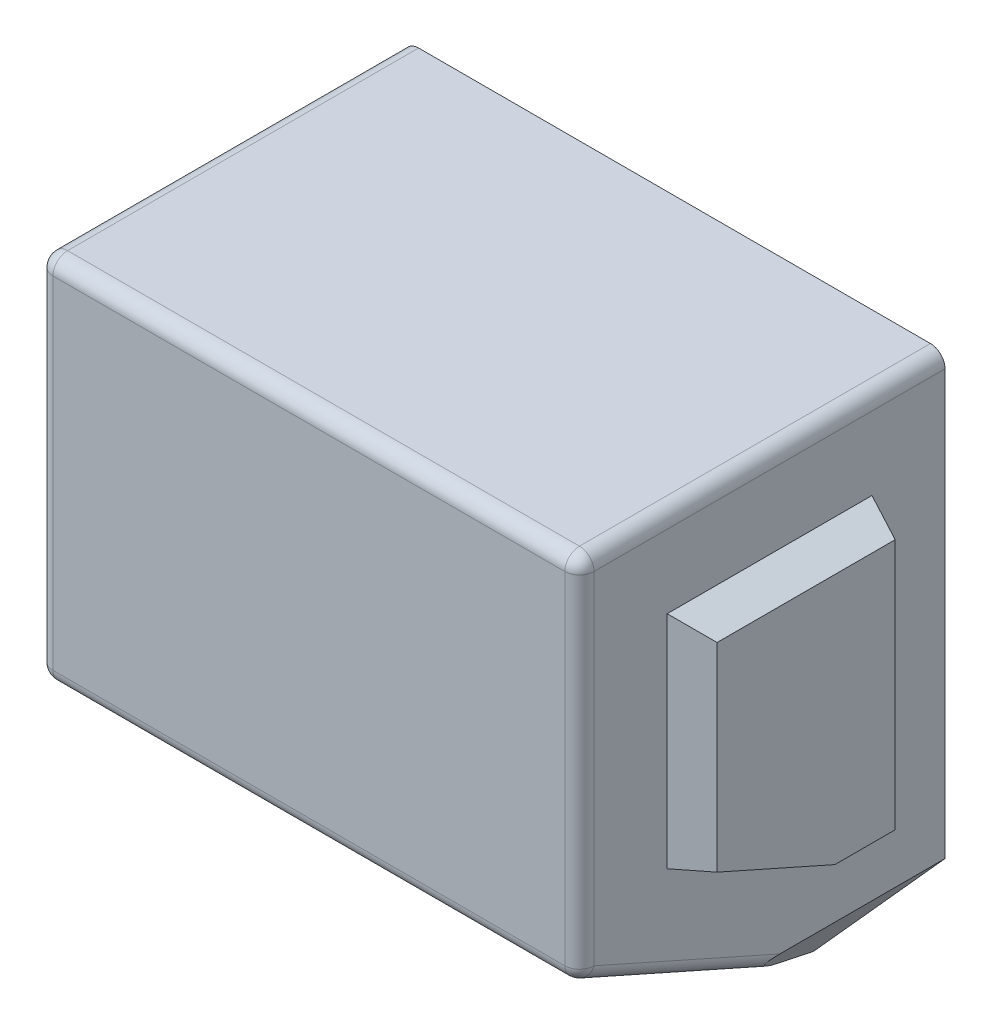
SolidWorks part; units mm, degrees
ref_plane "前视基准面" through (0, 0, 0) normal (0, 0, 1) x (1, 0, 0)
ref_plane "上视基准面" through (0, 0, 0) normal (0, 1, 0) x (1, 0, 0)
ref_plane "右视基准面" through (0, 0, 0) normal (1, 0, 0) x (0, 0, -1)
sketch "草图1" plane through (0, 0, 0) normal (1, 0, 0) x (0, 0, -1)
  line L0 (-50, 66) -> (0, 66)
  line L1 (0, 66) -> (0, 6)
  line L2 (0, 6) -> (-14, 0)
  line L3 (-14, 0) -> (-50, 16)
  line L4 (-50, 16) -> (-50, 66)
  point P2 (0, 15.2941)
  point P7 (0, 7.3671)
  point P8 (-19.5984, 0)
  point P9 (-11.7118, 14.0847)
  point P10 (-50, 39.1776)
  point P11 (-50, 32.2818)
  point P12 (-13.6613, 18.6053)
  point P13 (-50, 45.8435)
  point P14 (0, 0)
  point P15 (0.7049, 27.3399)
  dimension "D1" = 50
  dimension "D2" = 60
  dimension "D3" = 14
  dimension "D4" = 6
  dimension "D5" = 16
extrude "凸台-拉伸1" add sketch "草图1" along normal mid plane 74
sketch "草图5" plane through (0, 0, 0) normal (0, 0, -1) x (-1, 0, 0)
  line L8 (36, 7) -> (36, 65)
  line L9 (36, 65) -> (-36, 65)
  line L10 (-36, 65) -> (-36, 7)
  line L11 (-36, 7) -> (36, 7)
  line L12 (36, 7) -> (36, 65)
  line L13 (36, 65) -> (-36, 65)
  line L14 (-36, 65) -> (-36, 7)
  line L15 (-36, 7) -> (36, 7)
  dimension "D1" = 1
extrude "切除-拉伸1" cut sketch "草图5" against normal blind 2
sketch "草图6" plane through (0, 0, 2) normal (0, 0, -1) x (-1, 0, 0)
  line L8 (-33, 10) -> (33, 10)
  line L9 (33, 10) -> (33, 62)
  line L10 (33, 62) -> (-33, 62)
  line L11 (-33, 62) -> (-33, 10)
  line L12 (-33, 10) -> (33, 10)
  line L13 (33, 10) -> (33, 62)
  line L14 (33, 62) -> (-33, 62)
  line L15 (-33, 62) -> (-33, 10)
  dimension "D1" = 3
extrude "切除-拉伸2" cut sketch "草图6" against normal blind 2
sketch "草图9" plane through (0, 0, 0) normal (0, 0, -1) x (-1, 0, 0)
  line L0 (-37, 6) -> (-33, 0)
  line L1 (-37, 0) -> (37, 0) construction
  line L2 (-33, 0) -> (-37, 0)
  line L3 (-37, 0) -> (-37, 6)
  line L4 (0, 27.5) -> (0, -27.5) construction
  line L5 (33, 0) -> (37, 0)
  line L6 (37, 6) -> (33, 0)
  line L7 (37, 0) -> (37, 6)
  dimension "D1" = 4
extrude "切除-拉伸3" cut sketch "草图9" against normal through all
fillet "圆角1" radius 2 8 edges at (-37, 11, 38.75) (37, 11, 38.75) (0, 66, 50) (0, 16, 50) (-37, 41, 50) (37, 41, 50) (-37, 66, 25) (37, 66, 25)
sketch "草图10" plane through (0, 66, 0) normal (0, 1, 0) x (1, 0, 0)
  line L0 (35, -48.8123) -> (-35, -48.8123) construction
  line L1 (-32, -44) -> (32, -44)
  line L2 (-32, -44) -> (-32, -4)
  line L3 (-32, -4) -> (32, -4)
  line L4 (32, -44) -> (32, -4)
  line L5 (-35, -50) -> (35, -50) construction
  line L6 (37, 0) -> (-37, 0) construction
  point P6 (0, -48.8123)
  point P7 (0, -44)
  dimension "D1" = 64
  dimension "D2" = 6
  dimension "D3" = 4
extrude "切除-拉伸4" cut sketch "草图10" along normal blind 56 from offset 100 offset against normal yes
sketch "草图8" plane through (-37, 0, 0) normal (-1, 0, 0) x (0, 0, 1)
  line L10 (10, 16) -> (20.4534, 16)
  line L11 (10, 16) -> (20.4534, 16)
  line L12 (10, 54) -> (10, 16)
  line L13 (20.4534, 16) -> (38, 23.7985)
  line L14 (20.4534, 16) -> (38, 23.7985)
  line L17 (10, 54) -> (10, 16)
  line L20 (38, 23.7985) -> (38, 54)
  line L21 (38, 23.7985) -> (38, 54)
  line L22 (38, 54) -> (10, 54)
  line L23 (38, 54) -> (10, 54)
  dimension "D1" = 10
extrude "凸台-拉伸2" add sketch "草图8" along normal blind 5 draft 20
mirror "镜向1" about plane through (0, 0, 0) normal (1, 0, 0) of "凸台-拉伸2"
shell "抽壳1" thickness 2 removed face at (0, 26, 4) removed face at (0, 22, 24) removed face at (32, 11.9365, 19) removed face at (-32, 11.9365, 19) removed face at (0, 17.6667, 44)
